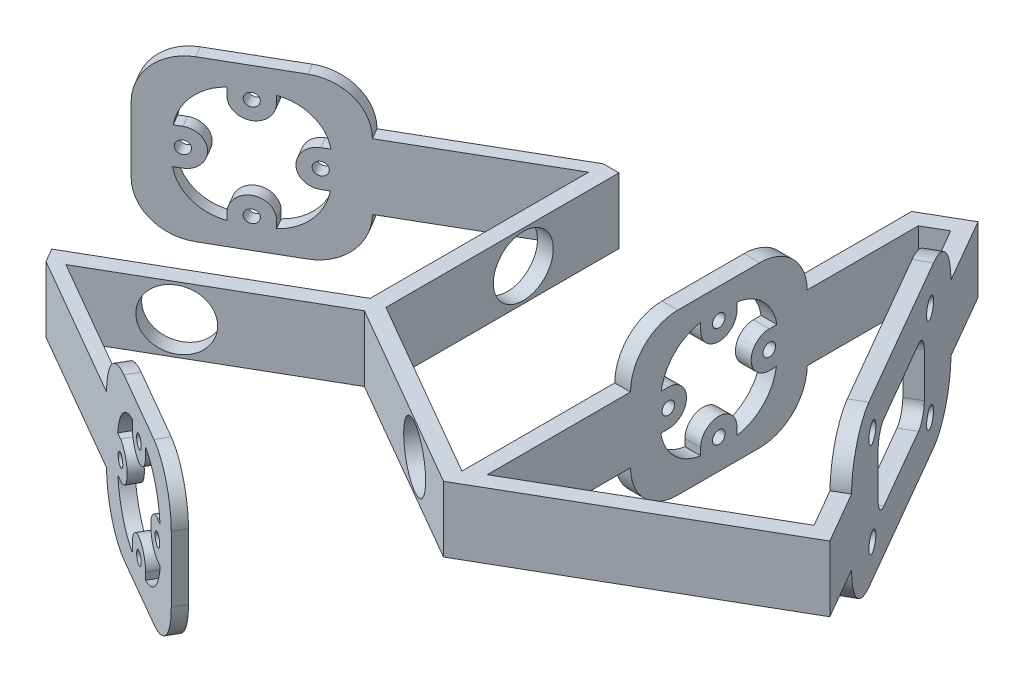
SolidWorks part; units mm, degrees
note: '?' marks a value the reader was unsure of.
material "2024 Alloy"
ref_plane "Front" through (0, 0, 0) normal (0, 0, 1) x (1, 0, 0)
ref_plane "Top" through (0, 0, 0) normal (0, 1, 0) x (1, 0, 0)
ref_plane "Right" through (0, 0, 0) normal (1, 0, 0) x (0, 0, -1)
sketch "Sketch1" plane through (0, 0, 0) normal (0, 1, 0) x (1, 0, 0)
  line L0 (0, 0) -> (0, 70) construction
  line L1 (0, 0) -> (-60.6218, -35) construction
  line L2 (0, 0) -> (60.6218, -35) construction
  line L3 (-2.5, 1.4434) -> (-2.5, 70)
  line L4 (-2.5, 70) -> (2.5, 70)
  line L5 (2.5, 70) -> (2.5, 1.4434)
  line L6 (-61.8718, -32.8349) -> (-2.5, 1.4434)
  line L7 (-61.8718, -32.8349) -> (-59.3718, -37.1651)
  line L8 (-59.3718, -37.1651) -> (0, -2.8868)
  line L9 (0, -2.8868) -> (59.3718, -37.1651)
  line L10 (59.3718, -37.1651) -> (61.8718, -32.8349)
  line L11 (61.8718, -32.8349) -> (2.5, 1.4434)
  line L12 (59.3718, -37.1651) -> (-59.3718, -37.1651) construction
  circle A0 centre (0, 0) radius 2.5 construction
  dimension "D4" = 5
  dimension "D1" = 120
  dimension "D2" = 120
  dimension "D3" = 70
extrude "Boss-Extrude1" add sketch "Sketch1" along normal blind 50.8
ref_axis "Axis1" through (0, 40.005, 0) along (0, -1, 0)?
sketch "Sketch3" plane through (1.25, 0, -2.1651) normal (-0.5, 0, 0.866) x (0.866, 0, 0.5)
  line L0 (45, 50.8) -> (45, 0) construction
  line L1 (1.4434, 50.8) -> (70, 50.8) construction
  line L2 (1.4434, 0) -> (70, 0) construction
  circle A0 centre (45, 25.4) radius 9.5
  dimension "D2" = 19
  dimension "D1" = 45
extrude "Cut-Extrude2" cut sketch "Sketch3" along normal blind 38.1
sketch "Sketch4" plane through (0, 50.8, 0) normal (0, 1, 0) x (1, 0, 0)
  line L0 (-2.5, 75.3442) -> (-96.4699, 21.0907)
  line L1 (-2.5, 1.4434) -> (-61.8718, -32.8349) construction
  line L2 (-96.4699, 21.0907) -> (-94.4699, 17.6266)
  line L3 (-94.4699, 17.6266) -> (-2.5, 70.7254)
  line L5 (-61.8718, -32.8349) -> (-59.3718, -37.1651) construction
  line L7 (-2.5, 75.3442) -> (2.5, 75.3442)
  line L8 (2.5, 75.3442) -> (2.5, 65)
  line L9 (-2.5, 70) -> (-2.5, 1.4434) construction
  line L11 (-2.5, 70.7254) -> (-2.5, 65)
  line L12 (-2.5, 65) -> (2.5, 65)
  line L13 (2.5, 1.4434) -> (2.5, 70) construction
  dimension "D1" = 60
  dimension "D2" = 3
  dimension "D3" = 4
  dimension "D4" = 65
extrude "Boss-Extrude2" add sketch "Sketch4" against normal up to surface (50.8 mm away) up to face at (0, 0, 0)
pattern_circular "CirPattern1" count 3 over 360 about axis through (0, 40.005, 0) along (0, -1, 0) of "Cut-Extrude2"
sketch "Sketch6" plane through (-33.25, 0, -57.5907) normal (0.5, 0, 0.866) x (0.866, 0, -0.5)
  line L10 (-50.75, 41.4) -> (-50.75, 43.8)
  line L11 (-50.75, 43.8) -> (-63.4, 43.8)
  line L12 (-63.4, 43.8) -> (-63.4, 31.15)
  line L13 (-63.4, 31.15) -> (-61, 31.15)
  line L14 (-70, 50.8) -> (-1.4434, 50.8) construction
  line L15 (-61, 19.65) -> (-63.4, 19.65)
  line L16 (-63.4, 19.65) -> (-63.4, 7)
  line L17 (-63.4, 7) -> (-50.75, 7)
  line L18 (-50.75, 7) -> (-50.75, 9.4)
  line L19 (-39.25, 9.4) -> (-39.25, 7)
  line L20 (-39.25, 7) -> (-26.6, 7)
  line L21 (-26.6, 7) -> (-26.6, 19.65)
  line L22 (-26.6, 19.65) -> (-29, 19.65)
  line L23 (-29, 31.15) -> (-26.6, 31.15)
  line L24 (-26.6, 31.15) -> (-26.6, 43.8)
  line L25 (-26.6, 43.8) -> (-39.25, 43.8)
  line L26 (-39.25, 43.8) -> (-39.25, 41.4)
  circle A0 centre (-45, 25.4) radius 16 construction
  circle A1 centre (-45, 41.4) radius 2
  circle A2 centre (-29, 25.4) radius 2
  circle A3 centre (-45, 9.4) radius 2
  circle A4 centre (-61, 25.4) radius 2
  arc A5 (-50.75, 41.4) -> (-39.25, 41.4) centre (-45, 41.4) ccw
  arc A19 (-29, 31.15) -> (-29, 19.65) centre (-29, 25.4) ccw
  arc A20 (-39.25, 9.4) -> (-50.75, 9.4) centre (-45, 9.4) ccw
  arc A21 (-61, 19.65) -> (-61, 31.15) centre (-61, 25.4) ccw
  dimension "D1" = 32
  dimension "D2" = 4
  dimension "D3" = 11.5
  dimension "D7" = 7
extrude "Cut-Extrude3" cut sketch "Sketch6" along normal up to surface (4 mm away) up to face at (-48.4849, 25.4, -44.176)
pattern_circular "CirPattern2" count 2 every 240 about axis through (0, 0, 0) along (0, 1, 0) of "Cut-Extrude3", "Boss-Extrude2"
sketch "Sketch5" plane through (0, 50.8, 0) normal (0, 1, 0) x (1, 0, 0)
  line L0 (59.3718, -37.1651) -> (137.024, 7.6675)
  line L1 (0, 45) -> (38.9711, -22.5) construction
  line L2 (59.5, -31.4656) -> (59.3718, -37.1651)
  line L3 (-2.5, 35.5) -> (2.5, 35.5)
  line L5 (61.8718, -32.8349) -> (2.5, 1.4434) construction
  line L6 (-2.5, 75.3442) -> (-96.4699, 21.0907) construction
  line L8 (72.8381, 118.8407) -> (137.024, 7.6675)
  line L9 (-2.5, 35.5) -> (2.5, 35.5) construction
  line L11 (2.5, 1.4434) -> (2.5, 75.3442) construction
  line L12 (59.5, -31.4656) -> (59.5, 111.1399)
  line L13 (59.5, 111.1399) -> (72.8381, 118.8407)
  line L17 (-2.5, 35.5) -> (-2.5, 54.5)
  line L18 (-2.5, 54.5) -> (2.5, 54.5)
  line L19 (2.5, 35.5) -> (2.5, 54.5)
  line L20 (-2.5, 35.5) -> (2.5, 54.5) construction
  line L21 (-2.5, 54.5) -> (2.5, 35.5) construction
  line L22 (45.9484, -29.4151) -> (29.4939, -19.9151)
  line L23 (45.9484, -29.4151) -> (48.4484, -25.0849)
  line L24 (48.4484, -25.0849) -> (31.9939, -15.5849)
  line L25 (29.4939, -19.9151) -> (31.9939, -15.5849)
  line L26 (45.9484, -29.4151) -> (31.9939, -15.5849) construction
  line L27 (48.4484, -25.0849) -> (29.4939, -19.9151) construction
  point P9 (0, 45)
  point P29 (38.9711, -22.5)
  dimension "D1" = 100
  dimension "D3" = 57
extrude "Boss-Extrude4" add sketch "Sketch5" against normal up to surface (50.8 mm away) up to face at (-13.3838, 0, 7.1639)
sketch "Sketch8" plane through (59.5, 0, 0) normal (1, 0, 0) x (0, 0, -1)
  line L0 (39.25, 41.4) -> (39.25, 43.8)
  line L1 (39.25, 43.8) -> (26.6, 43.8)
  line L2 (26.6, 43.8) -> (26.6, 31.15)
  line L3 (26.6, 31.15) -> (29, 31.15)
  line L4 (29, 19.65) -> (26.6, 19.65)
  line L5 (26.6, 19.65) -> (26.6, 7)
  line L6 (26.6, 7) -> (39.25, 7)
  line L7 (39.25, 7) -> (39.25, 9.4)
  line L8 (50.75, 9.4) -> (50.75, 7)
  line L9 (50.75, 7) -> (63.4, 7)
  line L10 (63.4, 7) -> (63.4, 19.65)
  line L11 (63.4, 19.65) -> (61, 19.65)
  line L12 (61, 31.15) -> (63.4, 31.15)
  line L13 (63.4, 31.15) -> (63.4, 43.8)
  line L14 (63.4, 43.8) -> (50.75, 43.8)
  line L15 (50.75, 43.8) -> (50.75, 41.4)
  line L16 (118.8407, 50.8) -> (7.6675, 50.8) construction
  circle A0 centre (45, 25.4) radius 9.5 construction
  circle A6 centre (45, 25.4) radius 16 construction
  circle A7 centre (45, 41.4) radius 2
  circle A8 centre (61, 25.4) radius 2
  circle A9 centre (45, 9.4) radius 2
  circle A10 centre (29, 25.4) radius 2
  arc A11 (39.25, 41.4) -> (50.75, 41.4) centre (45, 41.4) ccw
  arc A12 (61, 31.15) -> (61, 19.65) centre (61, 25.4) ccw
  arc A13 (50.75, 9.4) -> (39.25, 9.4) centre (45, 9.4) ccw
  arc A14 (29, 19.65) -> (29, 31.15) centre (29, 25.4) ccw
  dimension "D1" = 7
  dimension "D4" = 32
  dimension "D5" = 4
  dimension "D6" = 11.5
extrude "Cut-Extrude8" cut sketch "Sketch8" along normal blind 12.7
sketch "Sketch9" plane through (106.0881, 0, -61.25) normal (0.866, 0, -0.5) x (-0.5, 0, -0.866)
  line L1 (-25, 10.4) -> (25, 10.4) construction
  line L2 (-25, 10.4) -> (-25, 40.4) construction
  line L3 (-25, 40.4) -> (25, 40.4) construction
  line L4 (25, 10.4) -> (25, 40.4) construction
  line L5 (-25, 10.4) -> (25, 40.4) construction
  line L6 (-25, 40.4) -> (25, 10.4) construction
  line L8 (0, 0) -> (0, 50.8) construction
  line L10 (66.5, 50.8) -> (-61.8718, 50.8) construction
  line L12 (20, 13.4) -> (-20, 13.4)
  line L13 (20, 13.4) -> (20, 37.4)
  line L14 (20, 37.4) -> (-20, 37.4)
  line L15 (-20, 13.4) -> (-20, 37.4)
  line L16 (20, 13.4) -> (-20, 37.4) construction
  line L17 (20, 37.4) -> (-20, 13.4) construction
  circle A0 centre (-25, 40.4) radius 3
  circle A1 centre (25, 40.4) radius 3
  circle A2 centre (25, 10.4) radius 3
  circle A3 centre (-25, 10.4) radius 3
  point P0 (0, 25.4)
  point P14 (0, 25.4)
  dimension "D3" = 6
  dimension "D1" = 30
  dimension "D2" = 50
  dimension "D4" = 20
extrude "Cut-Extrude9" cut sketch "Sketch9" against normal blind 15
sketch "Sketch10" plane through (0, 50.8, 0) normal (0, 1, 0) x (1, 0, 0)
  line L0 (72.8381, 118.8407) -> (59.5, 111.1399) construction
  line L1 (59.5, 111.1399) -> (59.5, -31.4656) construction
  line L2 (59.5, -31.4656) -> (64.3718, -34.2783) construction
  line L3 (59.3718, -37.1651) -> (137.024, 7.6675) construction
  line L4 (64.3718, -34.2783) -> (137.024, 7.6675) construction
  line L5 (72.8381, 118.8407) -> (137.024, 7.6675) construction
  line L6 (137.024, 7.6675) -> (72.8381, 118.8407) construction
  line L8 (0, -2.8868) -> (59.3718, -37.1651) construction
  line L9 (71.008, 112.0106) -> (64.5, 108.2532)
  line L10 (64.5, 108.2532) -> (64.5, -28.4308)
  line L11 (64.5, -28.4308) -> (64.5, -28.4308)
  line L12 (64.5, -28.4308) -> (130.1939, 9.4976)
  line L13 (130.1939, 9.4976) -> (71.008, 112.0106)
  dimension "D1" = 5
extrude "Cut-Extrude10" cut sketch "Sketch10" against normal up to surface (50.8 mm away)
sketch "Sketch15" plane through (-33.25, 0, 57.5907) normal (-0.5, 0, 0.866) x (0.866, 0, 0.5)
  line L0 (61, 25.4) -> (29, 25.4) construction
  line L1 (-39.8372, 0) -> (17, 0)
  line L2 (-39.8372, 0) -> (-39.8372, 15)
  line L3 (-39.8372, 15) -> (17, 15)
  line L4 (17, 0) -> (17, 15)
  line L5 (-39.8372, 0) -> (17, 15) construction
  line L6 (-39.8372, 15) -> (17, 0) construction
  line L7 (45, 25.4) -> (45, 0) construction
  line L8 (-35.507, 0) -> (73, 0) construction
  line L9 (17, 5) -> (45, 5) construction
  line L10 (45, 5) -> (73, 5) construction
  line L11 (73, 0) -> (73, 50.8) construction
  point P4 (-11.4186, 7.5)
  dimension "D1" = 15
  dimension "D2" = 5
extrude "Cut-Extrude15" cut sketch "Sketch15" against normal up to vertex (69 mm away)
pattern_circular "CirPattern3" count 3 over 360 about axis through (0, 0, 0) along (0, 1, 0) of "Cut-Extrude15"
ref_plane "Plane2" through (14, 0, 24.2487) normal (-0.5, 0, -0.866) x (-0.866, 0, 0.5)
sketch "Sketch13" plane through (30.9359, 0, 53.5825) normal (0.5, 0, 0.866) x (0.866, 0, -0.5)
  line L1 (32.8349, 15) -> (122.5, 15)
  line L2 (32.8349, 15) -> (32.8349, 0)
  line L3 (32.8349, 0) -> (122.5, 0)
  line L4 (122.5, 15) -> (122.5, 0)
  line L5 (32.8349, 15) -> (122.5, 0) construction
  line L6 (32.8349, 0) -> (122.5, 15) construction
  point P4 (77.6675, 7.5)
extrude "Cut-Extrude13" cut sketch "Sketch13" against normal offset from surface (18.8718 mm away) 15 up to plane "Plane2"
sketch "Sketch14" plane through (0, 50.8, 0) normal (0, 1, 0) x (1, 0, 0)
  line L0 (2.5, 75.3442) -> (2.5, 1.4434)
  line L1 (2.5, 1.4434) -> (59.5, -31.4656)
  line L2 (-94.4699, 17.6266) -> (-2.5, 70.7254) construction
  line L3 (59.3718, -37.1651) -> (137.024, 7.6675)
  line L4 (59.3718, -37.1651) -> (0, -2.8868)
  line L5 (0, -2.8868) -> (-60, -37.5278)
  line L6 (-64, -39.8372) -> (-66.5, -35.507)
  line L7 (-66.5, -35.507) -> (-2.5, 1.4434)
  line L8 (-2.5, 1.4434) -> (-2.5, 70.7254)
  line L9 (-2.5, 75.3442) -> (2.5, 75.3442)
  line L10 (59.5, -31.4656) -> (59.5, 17)
  line L12 (59.5, 17) -> (64.5, 17)
  line L13 (59.5, 17) -> (64.5, 17) construction
  line L14 (64.5, 17) -> (64.5, -28.4308)
  line L15 (64.5, -28.4308) -> (130.1939, 9.4976) construction
  line L16 (64.5, -28.4308) -> (130.1939, 9.4976)
  line L17 (127.5881, 24.0109) -> (137.024, 7.6675)
  line L18 (-2.5, 75.3442) -> (-47.9724, 49.0907)
  line L19 (59.5, 73) -> (64.5, 73)
  line L20 (-47.9724, 49.0907) -> (-45.9724, 45.6266)
  line L21 (-45.9724, 45.6266) -> (-2.5, 70.7254)
  line L22 (64.5, 73) -> (64.5, 108.2532)
  line L23 (-64, -39.8372) -> (-18.5276, -66.0907)
  line L24 (-18.5276, -66.0907) -> (-16.5276, -62.6266)
  line L25 (-16.5276, -62.6266) -> (-60, -37.5278)
  line L26 (64.5, 108.2532) -> (71.008, 112.0106)
  line L27 (71.008, 112.0106) -> (80.258, 95.9891)
  line L28 (-16.5276, -62.6266) -> (-18.5276, -66.0907) construction
  line L29 (130.1939, 9.4976) -> (71.008, 112.0106) construction
  line L30 (59.5, 43) -> (64.5, 43) construction
  line L31 (80.258, 95.9891) -> (84.5881, 98.4891)
  line L32 (72.8381, 118.8407) -> (137.024, 7.6675) construction
  line L33 (84.5881, 98.4891) -> (72.8381, 118.8407)
  line L34 (-45.9724, 45.6266) -> (-47.9724, 49.0907) construction
  line L36 (64.5, 47) -> (59.5, 47) construction
  line L37 (72.8381, 118.8407) -> (59.5, 111.1399)
  line L38 (59.5, 111.1399) -> (59.5, 73)
  line L39 (92.0881, 85.4987) -> (87.758, 82.9987) construction
  line L40 (130.1939, 9.4976) -> (123.258, 21.5109)
  line L41 (123.258, 21.5109) -> (127.5881, 24.0109)
  line L42 (115.758, 34.5013) -> (120.0881, 37.0013) construction
  line L43 (62, 43) -> (62, 17) construction
  line L44 (-2.5, 75.3442) -> (-96.4699, 21.0907) construction
  line L45 (62, 73) -> (62, 47) construction
  line L46 (2.5, 75.3442) -> (-2.5, 75.3442) construction
  line L47 (-66.5, -35.507) -> (-64, -39.8372) construction
  line L48 (-64, -39.8372) -> (29.9699, -94.0907) construction
  dimension "D1" = 15
  dimension "D2" = 15
extrude "Cut-Extrude14" cut sketch "Sketch14" against normal blind 15
sketch "Sketch16" plane through (0, 0, 0) normal (0, -1, 0) x (1, 0, 0)
  line L0 (59.5, -73) -> (64.5, -73)
  line L1 (64.5, -108.2532) -> (64.5, -17) construction
  line L2 (64.5, -108.2532) -> (71.008, -112.0106)
  line L3 (71.008, -112.0106) -> (80.258, -95.9891)
  line L4 (80.258, -95.9891) -> (84.5881, -98.4891)
  line L5 (84.5881, -98.4891) -> (72.8381, -118.8407)
  line L6 (72.8381, -118.8407) -> (59.5, -111.1399)
  line L7 (59.5, -111.1399) -> (59.5, -73)
  line L8 (64.5, -73) -> (64.5, -108.2532)
  line L9 (59.5, -17) -> (64.5, -17)
  line L10 (59.5, -17) -> (59.5, 28.4308)
  line L12 (59.5, 28.4308) -> (64.5, 28.4308)
  line L13 (64.5, 28.4308) -> (64.5, -17)
  line L14 (59.5, 28.4308) -> (64.5, -17) construction
  point P20 (62.9377, -2.8046)
extrude "Cut-Extrude16" cut sketch "Sketch16" against normal up to surface (15 mm away)
fillet "Fillet2" radius 15 112 edges at (-87.156, 43.8, -24.1586) (-88.156, 37.475, -25.8907) (-87.156, 31.15, -24.1586) (-88.156, 13.325, -25.8907) (-87.156, 7, -24.1586) (-82.6784, 7, -29.0532) (-76.2008, 7, -30.4836) (-61.7639, 7, -41.1282) (-55.2863, 7, -42.5586) (-56.2863, 13.325, -44.2907) (-55.2863, 19.65, -42.5586) (-56.2863, 37.475, -44.2907) (-55.2863, 43.8, -42.5586) (-61.7639, 43.8, -41.1282) (-66.2415, 43.8, -36.2336) (-80.6784, 43.8, -25.5891) (-86.156, 37.475, -22.4266) (-86.156, 13.325, -22.4266) (-80.6784, 7, -25.5891) (-59.7639, 7, -37.6641) (-54.2863, 13.325, -40.8266) (-54.2863, 37.475, -40.8266) (-59.7639, 43.8, -37.6641) (30.9699, 50.8, 92.3586) (30.9699, 0, 92.3586) (16.1784, 43.8, 86.1282) (22.656, 43.8, 87.5586) (21.656, 37.475, 89.2907) (22.656, 31.15, 87.5586) (21.656, 13.325, 89.2907) (22.656, 7, 87.5586) (16.1784, 7, 86.1282) (11.7008, 7, 81.2336) (-4.7361, 7, 74.0532) (-9.2137, 7, 69.1586) (-10.2137, 13.325, 70.8907) (-9.2137, 19.65, 69.1586) (-10.2137, 37.475, 70.8907) (-9.2137, 43.8, 69.1586) (-4.7361, 43.8, 74.0532) (1.7415, 43.8, 75.4836) (18.1784, 43.8, 82.6641) (23.656, 37.475, 85.8266) (23.656, 13.325, 85.8266) (18.1784, 7, 82.6641) (-2.7361, 7, 70.5891) (-8.2137, 13.325, 67.4266) (-8.2137, 37.475, 67.4266) (-2.7361, 43.8, 70.5891) (59.5, 43.8, -32.925) (59.5, 37.475, -26.6) (59.5, 13.325, -26.6) (59.5, 7, -32.925) (59.5, 7, -57.075) (59.5, 13.325, -63.4) (59.5, 37.475, -63.4) (59.5, 43.8, -57.075) (62, 43.8, -50.75) (62, 43.8, -63.4) (62, 19.65, -63.4) (62, 7, -63.4) (62, 7, -39.25) (62, 7, -26.6) (-95.4699, 50.8, -19.3586) (62, 31.15, -26.6) (62, 43.8, -26.6) (64.5, 43.8, -57.075) (64.5, 37.475, -63.4) (64.5, 13.325, -63.4) (64.5, 7, -57.075) (64.5, 7, -32.925) (64.5, 13.325, -26.6) (64.5, 37.475, -26.6) (64.5, 43.8, -32.925) (-95.4699, 0, -19.3586) (-16.5276, 7.5, 62.6266) (-17.5276, 0, 64.3586) (-18.5276, 7.5, 66.0907) (64.5, 7.5, -17) (59.5, 7.5, -17) (62, 0, -17) (-45.9724, 7.5, -45.6266) (-46.9724, 0, -47.3586) (-47.9724, 7.5, -49.0907) (123.258, 7.5, -21.5109) (125.423, 0, -22.7609) (127.5881, 7.5, -24.0109) (59.5, 43.3, -17) (64.5, 43.3, -17) (123.258, 43.3, -21.5109) (127.5881, 43.3, -24.0109) (-16.5276, 43.3, 62.6266) (-18.5276, 43.3, 66.0907) (-45.9724, 43.3, -45.6266) (-47.9724, 43.3, -49.0907) (-46.9724, 50.8, -47.3586) (-17.5276, 50.8, 64.3586) (125.423, 50.8, -22.7609) (62, 50.8, -17) (59.5, 43.3, -73) (84.5881, 43.3, -98.4891) (80.258, 43.3, -95.9891) (64.5, 43.3, -73) (62, 50.8, -73) (82.423, 50.8, -97.2391) (82.423, 0, -97.2391) (62, 0, -73) (84.5881, 7.5, -98.4891) (80.258, 7.5, -95.9891) (64.5, 7.5, -73) (59.5, 7.5, -73) (-82.6784, 43.8, -29.0532)
fillet "Fillet3" radius 5 4 edges at (93.923, 37.4, -77.3205) (93.923, 13.4, -77.3205) (113.923, 13.4, -42.6795) (113.923, 37.4, -42.6795)
